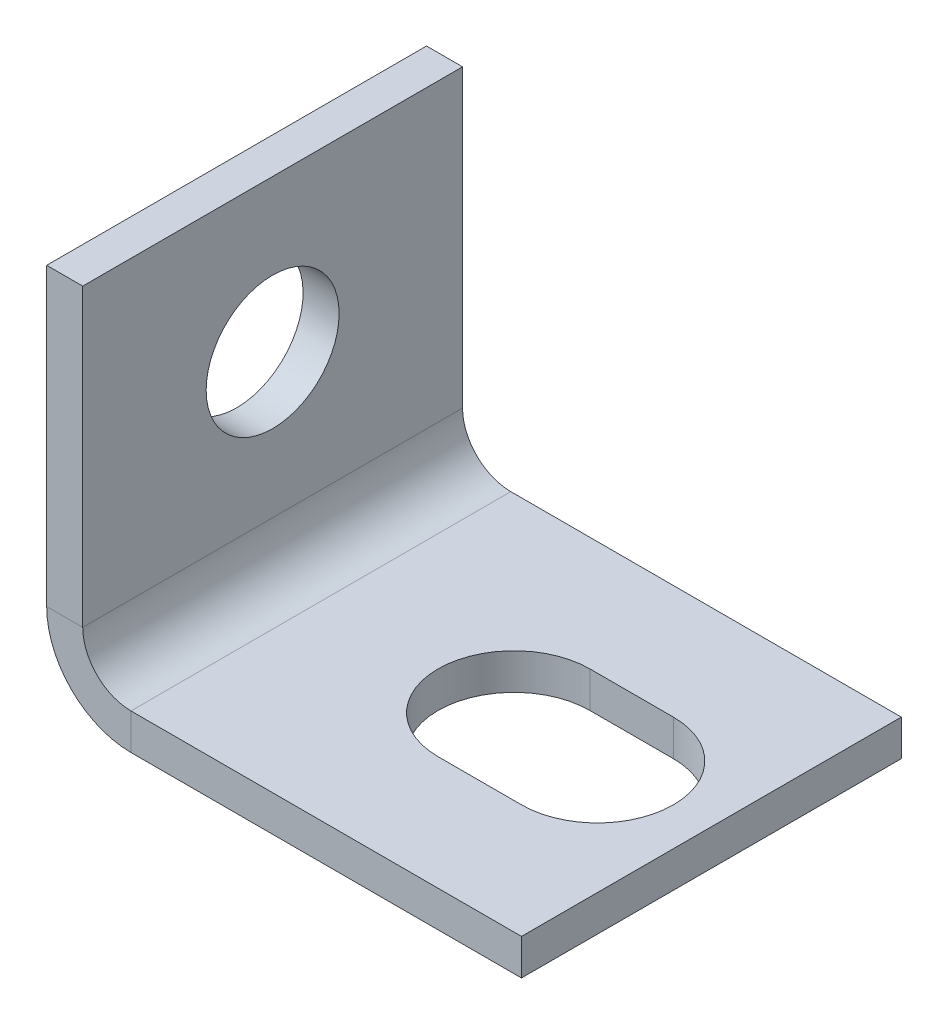
SolidWorks part; units mm, degrees
note: The reader was unsure of these and kept them because the rebuilt part matched: flange length of "Edge-Flange1".
ref_plane "Front Plane" through (0, 0, 0) normal (0, 0, 1) x (1, 0, 0)
ref_plane "Top Plane" through (0, 0, 0) normal (0, 1, 0) x (1, 0, 0)
ref_plane "Right Plane" through (0, 0, 0) normal (1, 0, 0) x (0, 0, -1)
sketch "Sketch2" plane through (0, 3.2694, 0) normal (0, 1, 0) x (1, 0, 0)
  line L1 (-38.2833, -381.1367) -> (-13.2833, -381.1367)
  line L2 (-38.2833, -381.1367) -> (-38.2833, -401.1367)
  line L3 (-38.2833, -401.1367) -> (-13.2833, -401.1367)
  line L4 (-13.2833, -381.1367) -> (-13.2833, -401.1367)
  dimension "D1" = 20
  dimension "D2" = 25
base flange "Base-Flange1" sketch "Sketch2" thickness 1.8974 reverse thickness direction yes parameters "D1"=2.54
edge flange "Edge-Flange1" sketch "Sketch9" flange angle 90 flange length 20 flange position material inside bend radius 2.54 thickness 1.8974 relief rectangular parameters "D1"=3.175, "D6"=10
sketch "Sketch9" plane through (-38.2833, 5.1668, 0) normal (-1, 0, 0) x (0, 0, 1)
  line L2 (381.1367, 0) -> (381.1367, 18.1026)
  line L3 (381.1367, 18.1026) -> (401.1367, 18.1026)
  line L4 (401.1367, 18.1026) -> (401.1367, 0)
  line L5 (381.1367, 0) -> (401.1367, 0) construction
  line L6 (381.1367, 0) -> (401.1367, 0)
bend "EdgeBend1" bend radius 2.54 bend angle 90 parameters "D5"=1
sketch "Sketch11" plane through (-38.2833, 0, 0) normal (-1, 0, 0) x (0, 0, 1)
  line L0 (391.1367, 9.8535) -> (391.1367, 20.6853) construction
  line L3 (356.1367, 15.2694) -> (401.1367, 15.2694) construction
  line L5 (401.1367, 7.7068) -> (401.1367, 23.2694) construction
  line L6 (401.1367, 15.2694) -> (401.1367, 22.2045) construction
  line L7 (401.1367, 23.2694) -> (381.1367, 23.2694) construction
  circle A0 centre (391.1367, 15.2694) radius 3.5
  point P4 (391.1367, 23.2694)
  point P5 (391.1367, 15.2694)
  dimension "D1" = 7
  dimension "D3" = 8
  dimension "D4" = 8
extrude "Cut-Extrude1" cut sketch "Sketch11" against normal blind 10 normal cut yes
sketch "Sketch13" plane through (0, 5.1668, 0) normal (0, 1, 0) x (1, 0, 0)
  line L0 (-13.2833, -401.1367) -> (-13.2833, -381.1367) construction
  line L1 (-23.6788, -391.1367) -> (-19.2833, -391.1367) construction
  line L2 (-23.6788, -387.1367) -> (-19.2833, -387.1367)
  line L3 (-23.6788, -395.1367) -> (-19.2833, -395.1367)
  arc A0 (-23.6788, -387.1367) -> (-23.6788, -395.1367) centre (-23.6788, -391.1367) ccw
  arc A1 (-19.2833, -395.1367) -> (-19.2833, -387.1367) centre (-19.2833, -391.1367) ccw
  point P2 (-13.2833, -391.1367)
  point P3 (-21.4811, -391.1367)
  dimension "D1" = 6
extrude "Cut-Extrude2" cut sketch "Sketch13" against normal blind 10 normal cut yes
sketch "Bend-Lines1" [suppressed] plane through (0, 0, 0) normal (0, 1, 0) x (1, 0, 0)
sketch "Bounding-Box1" [suppressed] plane through (0, 0, 0) normal (0, 1, 0) x (1, 0, 0)
sheet metal parameters "Sheet-Metal1" thickness 1.8974 parameters "D1"=3.175
flat pattern "Flat-Pattern1" [suppressed]
sketch "Bend-Lines2" plane through (0, 0, 0) normal (0, 1, 0) x (1, 0, 0)
sketch "Bounding-Box2" [suppressed] plane through (0, 0, 0) normal (0, 1, 0) x (1, 0, 0)
sheet metal parameters "Sheet-Metal2" thickness 1.8974 parameters "D1"=3.175
flat pattern "Flat-Pattern1" [suppressed]
sketch "Bend-Lines2" plane through (0, 0, 0) normal (0, 1, 0) x (1, 0, 0)
sketch "Bounding-Box2" [suppressed] plane through (0, 0, 0) normal (0, 1, 0) x (1, 0, 0)
bend of the flat pattern "Flatten-<EdgeBend1>1"
sheet metal parameters "Sheet-Metal3" thickness 1.8974 parameters "D1"=3.175
flat pattern "Flat-Pattern1"
sketch "Bend-Lines2" plane through (0, 3.2694, 0) normal (0, -1, 0) x (-1, 0, 0)
  line L0 (35.9885, -401.1367) -> (35.9885, -381.1367) construction
  line L1 (35.9885, -401.1367) -> (35.9885, -381.1367) construction
sketch3d "Bounding-Box2" [suppressed]
  line L0 (13.2833, -401.1367, 0) -> (58.6936, -401.1367, 0) construction
  line L1 (13.2833, -381.1367, 0) -> (58.6936, -381.1367, 0) construction
  line L2 (13.2833, -401.1367, 0) -> (13.2833, -381.1367, 0) construction
  line L3 (58.6936, -401.1367, 0) -> (58.6936, -381.1367, 0) construction
bend of the flat pattern "Flatten-<EdgeBend1>1"
sheet metal parameters "Sheet-Metal4" thickness 1.8974 parameters "D1"=3.175
flat pattern "Flat-Pattern1"
sketch "Bend-Lines2" plane through (0, 3.2694, 0) normal (0, -1, 0) x (-1, 0, 0)
  line L0 (36.586, -401.1367) -> (36.586, -381.1367) construction
  line L1 (36.586, -401.1367) -> (36.586, -381.1367) construction
sketch3d "Bounding-Box2" [suppressed]
  line L0 (13.2833, -401.1367, 0) -> (54.8886, -401.1367, 0) construction
  line L1 (13.2833, -381.1367, 0) -> (54.8886, -381.1367, 0) construction
  line L2 (13.2833, -401.1367, 0) -> (13.2833, -381.1367, 0) construction
  line L3 (54.8886, -401.1367, 0) -> (54.8886, -381.1367, 0) construction
bend of the flat pattern "Flatten-<EdgeBend1>1"
